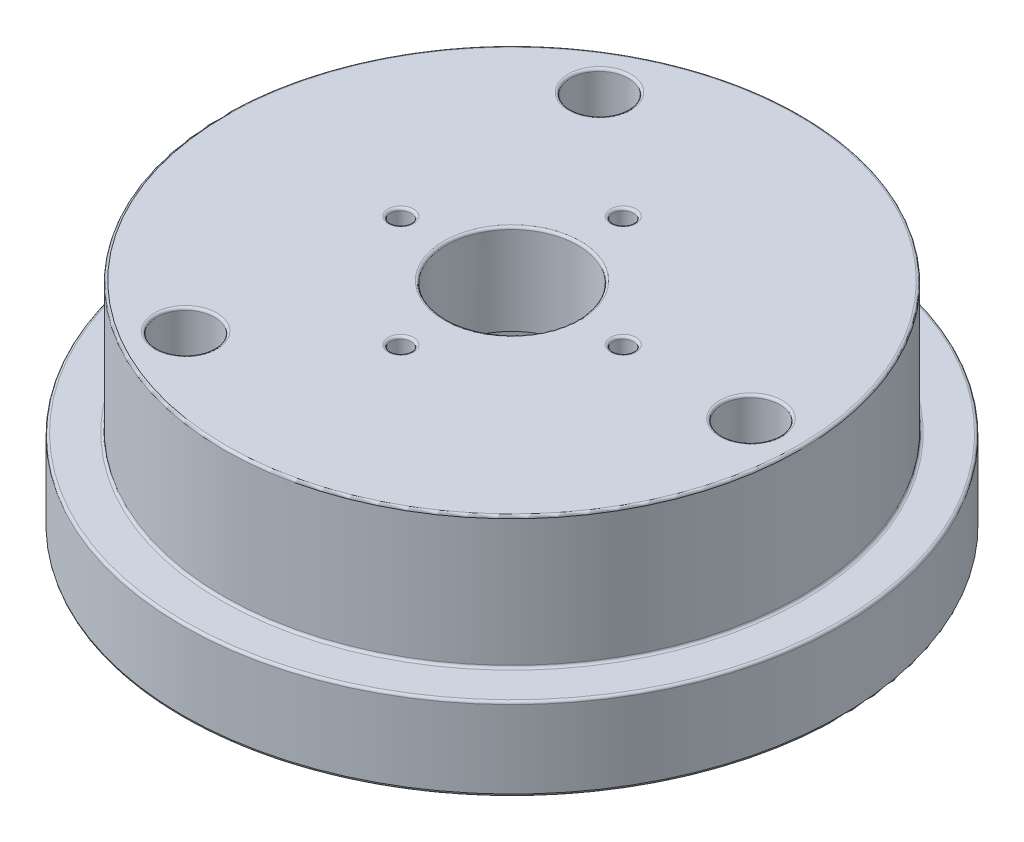
SolidWorks part; units mm, degrees
ref_plane "Front" through (0, 0, 0) normal (0, 0, 1) x (1, 0, 0)
ref_plane "Top" through (0, 0, 0) normal (0, 1, 0) x (1, 0, 0)
ref_plane "Right" through (0, 0, 0) normal (1, 0, 0) x (0, 0, -1)
sketch "Sketch1" plane through (0, 0, 0) normal (0, 0, 1) x (1, 0, 0)
  line L0 (0, 0) -> (-20, 0)
  line L1 (-20, 0) -> (-20, 5)
  line L2 (-20, 5) -> (-17.5, 5)
  line L3 (-17.5, 5) -> (-17.5, 13)
  line L4 (-17.5, 13) -> (0, 13)
  line L5 (0, 13) -> (0, 0)
  dimension "D1" = 13
  dimension "D2" = 5
  dimension "D3" = 20
  dimension "D4" = 17.5
revolve "Revolve1" add sketch "Sketch1" angle 360 about L5
sketch "Sketch2" plane through (0, 0, 0) normal (0, -1, 0) x (1, 0, 0)
  circle A0 centre (0, 0) radius 10
  circle A1 centre (14.5, 0) radius 1.75
  circle A2 centre (-7.25, -12.5574) radius 1.75
  circle A3 centre (-7.25, 12.5574) radius 1.75
  circle A4 centre (0, 0) radius 20 construction
  circle A5 centre (0, 0) radius 4
  circle A6 centre (6.75, 0) radius 0.625
  circle A7 centre (0, -6.75) radius 0.625
  circle A8 centre (-6.75, 0) radius 0.625
  circle A9 centre (0, 6.75) radius 0.625
  point P12 (0, 0)
  point P24 (0, 0)
  dimension "D1" = 20
  dimension "D2" = 3.5
  dimension "D5" = 8
  dimension "D6" = 1.25
  dimension "D3" = 14.5
  dimension "D7" = 6.75
  dimension "D4" = 3
  dimension "D8" = 4
extrude "Cut-Extrude1" cut sketch "Sketch2" against normal through all contours A2 | A5 | A8 | A7 | A9 | A6 | A1 | A3 region at (14.5, 0, 0) region at (-7.25, 0, -12.5574) region at (-7.25, 0, 12.5574) region at (0, 0, 0) region at (6.75, 0, 0) region at (0, 0, -6.75) region at (-6.75, 0, 0) region at (0, 0, 6.75)
extrude "Cut-Extrude2" cut sketch "Sketch2<3>" against normal blind 7.5 contours A0
sketch "Sketch2<3>" plane through (0, 0, 0) normal (0, -1, 0) x (1, 0, 0) same geometry as "Sketch2"
fillet "Fillet1" radius 0.15 16 edges at (0, 13, 17.5) (0, 13, 6.125) (0, 13, -7.375) (-6.75, 13, -0.625) (0, 13, -4) (6.75, 13, -0.625) (14.5, 13, -1.75) (-7.25, 13, 10.8074) (-7.25, 13, -14.3074) (0, 5, 17.5) (0, 5, 20) (0, 0, 20) (14.5, 0, -1.75) (-7.25, 0, 10.8074) (-7.25, 0, -14.3074) (0, 0, -10)
